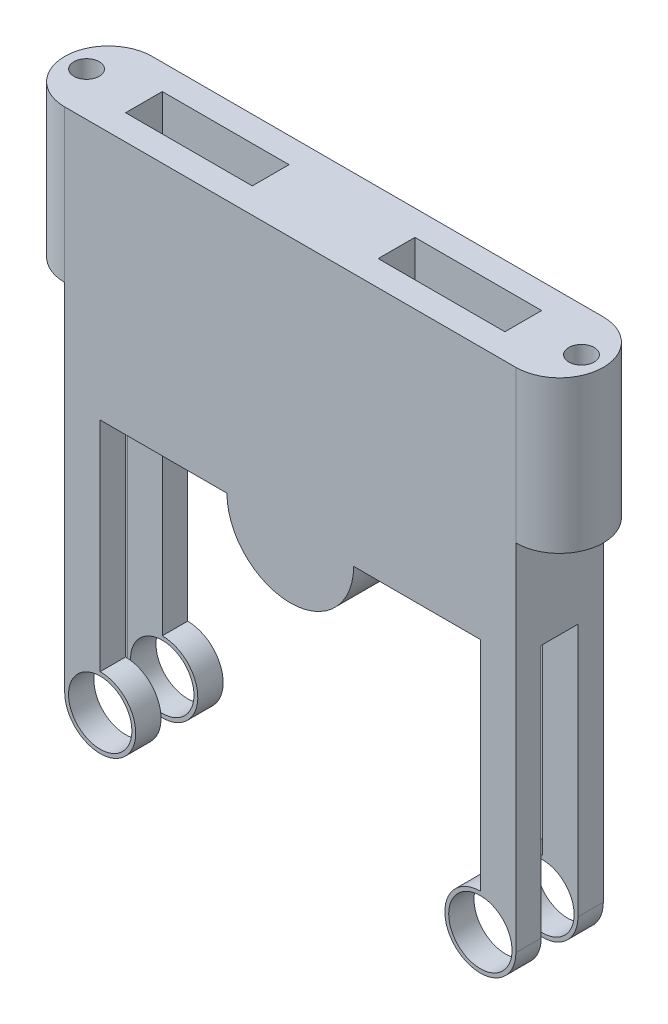
SolidWorks part; units mm, degrees
ref_plane "Front Plane" through (0, 0, 0) normal (0, 0, 1) x (1, 0, 0)
ref_plane "Top Plane" through (0, 0, 0) normal (0, 1, 0) x (1, 0, 0)
ref_plane "Right Plane" through (0, 0, 0) normal (1, 0, 0) x (0, 0, -1)
sketch "Sketch1" plane through (0, 0, 0) normal (0, 1, 0) x (1, 0, 0)
  line L0 (-9.525, 0.9208) -> (-9.525, -0.9207)
  line L2 (10.033, -0.9207) -> (10.033, 0.9208)
  line L4 (-10.033, -0.9208) -> (-10.033, 0.9207)
  line L9 (9.4837, 0.9208) -> (9.4837, -0.9207)
  line L10 (11.3047, 2.1907) -> (-11.3047, 2.1907)
  line L11 (2.6257, 0.9208) -> (2.6257, -0.9207)
  line L12 (11.3047, 2.1907) -> (11.3047, -2.1907)
  line L13 (11.3047, -2.1907) -> (-11.3047, -2.1907)
  line L14 (-11.3047, 2.1907) -> (-11.3047, -2.1907)
  line L15 (11.3047, 2.1907) -> (-11.3047, -2.1907) construction
  line L16 (11.3047, -2.1907) -> (-11.3047, 2.1907) construction
  line L17 (-9.525, 0.9208) -> (-3.175, 0.9208)
  line L18 (-9.525, 0.9208) -> (-9.525, -0.9207)
  line L19 (-9.525, -0.9207) -> (-3.175, -0.9207)
  line L20 (-3.175, 0.9208) -> (-3.175, -0.9207)
  line L21 (9.4837, 0.9208) -> (3.1337, 0.9208)
  line L22 (9.4837, 0.9208) -> (9.4837, -0.9207)
  line L23 (9.4837, -0.9207) -> (3.1337, -0.9207)
  line L24 (3.1337, 0.9208) -> (3.1337, -0.9207)
  line L26 (-3.175, 0.9208) -> (-3.175, -0.9207)
  line L28 (-2.667, 0.9208) -> (-2.667, -0.9207)
  point P0 (0, 0)
  point P6 (0, 0)
  point P7 (0, 0)
  point P8 (0, 0)
  point P14 (0, 0)
  dimension "D1" = 1.8415
  dimension "D2" = 20.066
  dimension "D3" = 6.35
  dimension "D4" = 6.35
  dimension "D5" = 0.508
  dimension "D6" = 0.508
  dimension "D7" = 4.3815
extrude "Boss-Extrude1" add sketch "Sketch1" along normal blind 6.35 contours L10 L14 L13 L12 L24 L21 L9 L23 L17 L20 L19 L0 region at (0.0064, 0, 0)
ref_plane "Plane1" through (0, 0, 0) normal (0, 0, 1) x (1, 0, 0)
sketch "Sketch2" plane through (0, 0, 0) normal (0, 0, 1) x (1, 0, 0)
  line L0 (3.175, 0) -> (-3.175, 0)
  line L1 (11.3047, 0) -> (-11.3047, 0) construction
  arc A0 (-3.175, 0) -> (3.175, 0) centre (0, 0) ccw
  point P6 (0, 0)
  dimension "D1" = 6.35
extrude "Boss-Extrude2" add sketch "Sketch2" against normal up to surface (2.1907 mm away) up to face at (0, 3.175, -2.1907)
extrude "Boss-Extrude3" add sketch "Sketch2<3>" along normal up to surface (2.1907 mm away) up to face at (0, 3.175, 2.1907)
sketch "Sketch2<3>" plane through (0, 0, 0) normal (0, 0, 1) x (1, 0, 0) same geometry as "Sketch2"
sketch "Sketch6" plane through (0, 0, 0) normal (0, -1, 0) x (1, 0, 0)
  line L0 (-9.525, 0.9207) -> (-11.3047, 0.9207)
  line L1 (-11.3047, -2.1907) -> (-11.3047, 2.1907) construction
  line L2 (9.4837, 0.9207) -> (11.3047, 0.9207)
  line L3 (11.3047, -2.1907) -> (11.3047, 2.1907) construction
sketch "Sketch7" plane through (0, 0, 2.1907) normal (0, 0, 1) x (1, 0, 0)
  line L0 (-11.3047, 0) -> (-11.3047, -12.7)
  line L2 (-9.525, 0) -> (-11.3047, 0)
  line L5 (-11.3047, 0) -> (-11.3047, -12.7)
  line L6 (-9.525, 0) -> (-9.525, -10.9203)
  circle A0 centre (-9.525, -12.7) radius 1.5875
  arc A2 (-11.3047, -12.7) -> (-9.525, -10.9203) centre (-9.525, -12.7) ccw
  point P11 (-7.9375, -12.7)
  point P12 (-7.9375, -12.7)
  point P13 (-9.525, -11.1125)
  point P15 (-11.1125, -12.7)
  line M12 (-11.3047, 0) -> (-3.175, 0)
  dimension "D1" = 12.7
extrude "Boss-Extrude4" add sketch "Sketch7" against normal blind 1.27 contours L0 A2 L6 A0 M12 region at (-10.3483, -6.3045, 2.1907)
mirror "Mirror1" about plane through (0, 0, 0) normal (1, 0, 0) of "Boss-Extrude4"
mirror "Mirror2" about plane through (0, 0, 0) normal (0, 0, 1) of "Mirror1"
sketch "Sketch8" plane through (0, 6.35, 0) normal (0, 1, 0) x (1, 0, 0)
  line L0 (-11.3047, 2.1907) -> (-11.3047, -2.1907)
  line L1 (0, 0) -> (0, 2.1907) construction
  line L3 (11.3047, 2.1907) -> (-11.3047, 2.1907) construction
  line L5 (11.3047, 2.1908) -> (11.3047, -2.1907)
  arc A0 (-11.3047, 2.1907) -> (-11.3047, -2.1907) centre (-11.3047, 0) ccw
  circle A1 centre (12.4001, 0) radius 0.635
  circle A2 centre (-12.4001, 0) radius 0.635
  arc A3 (11.3047, 2.1908) -> (11.3047, -2.1907) centre (11.3047, 0) cw
  dimension "D1" = 1.27
extrude "Boss-Extrude5" add sketch "Sketch8" against normal blind 1.27 and the other way blind 6.35
sketch "Sketch9" plane through (0, 0, -2.1907) normal (0, 0, -1) x (-1, 0, 0)
  line L0 (11.3047, 6.35) -> (11.3047, 12.7)
  line L2 (-11.3047, 6.35) -> (11.3047, 6.35)
  line L3 (-11.3047, 6.35) -> (-11.3047, 12.7)
  line L4 (-11.3047, 12.7) -> (11.3047, 12.7)
  line L5 (11.3047, 6.35) -> (11.3047, 12.7)
  dimension "D1" = 6.35
extrude "Boss-Extrude6" add sketch "Sketch9" against normal up to surface (4.3815 mm away) contours L3 L2 L5 L4 up to face at (0, -2.6543, 2.1907)
sketch "Sketch10" plane through (0, 12.7, 0) normal (0, 1, 0) x (1, 0, 0)
  line L1 (-9.525, 0.9208) -> (-3.175, 0.9208)
  line L2 (-9.525, 0.9208) -> (-9.525, -0.9207)
  line L3 (-9.525, -0.9207) -> (-3.175, -0.9207)
  line L4 (-3.175, 0.9208) -> (-3.175, -0.9207)
  line L5 (3.1337, 0.9208) -> (9.4837, 0.9208)
  line L6 (3.1337, 0.9208) -> (3.1337, -0.9207)
  line L7 (3.1337, -0.9207) -> (9.4837, -0.9207)
  line L8 (9.4837, 0.9208) -> (9.4837, -0.9207)
extrude "Cut-Extrude1" cut sketch "Sketch10" against normal up to surface (12.7 mm away) contours L8 L5 L6 L7 | L2 L1 L4 L3 region at (6.3087, 12.7, 0) up to face at (-6.35, 0, 1.5557)
sketch "Sketch11" plane through (0, 12.7, 0) normal (0, 1, 0) x (1, 0, 0)
  line L0 (-11.3047, 2.1907) -> (-11.3047, -2.1907) construction
  line L1 (-11.3047, 2.1907) -> (-11.3047, -2.1907)
  line L2 (0, 0) -> (0, 2.1907) construction
  line L3 (11.3047, 2.1908) -> (11.3047, -2.1907)
  circle A0 centre (-12.4001, 0) radius 0.635
  arc A1 (-11.3047, 2.1907) -> (-11.3047, -2.1907) centre (-11.3047, 0) ccw
  arc A2 (11.3047, 2.1908) -> (11.3047, -2.1907) centre (11.3047, 0) cw
  circle A3 centre (12.4001, 0) radius 0.635
